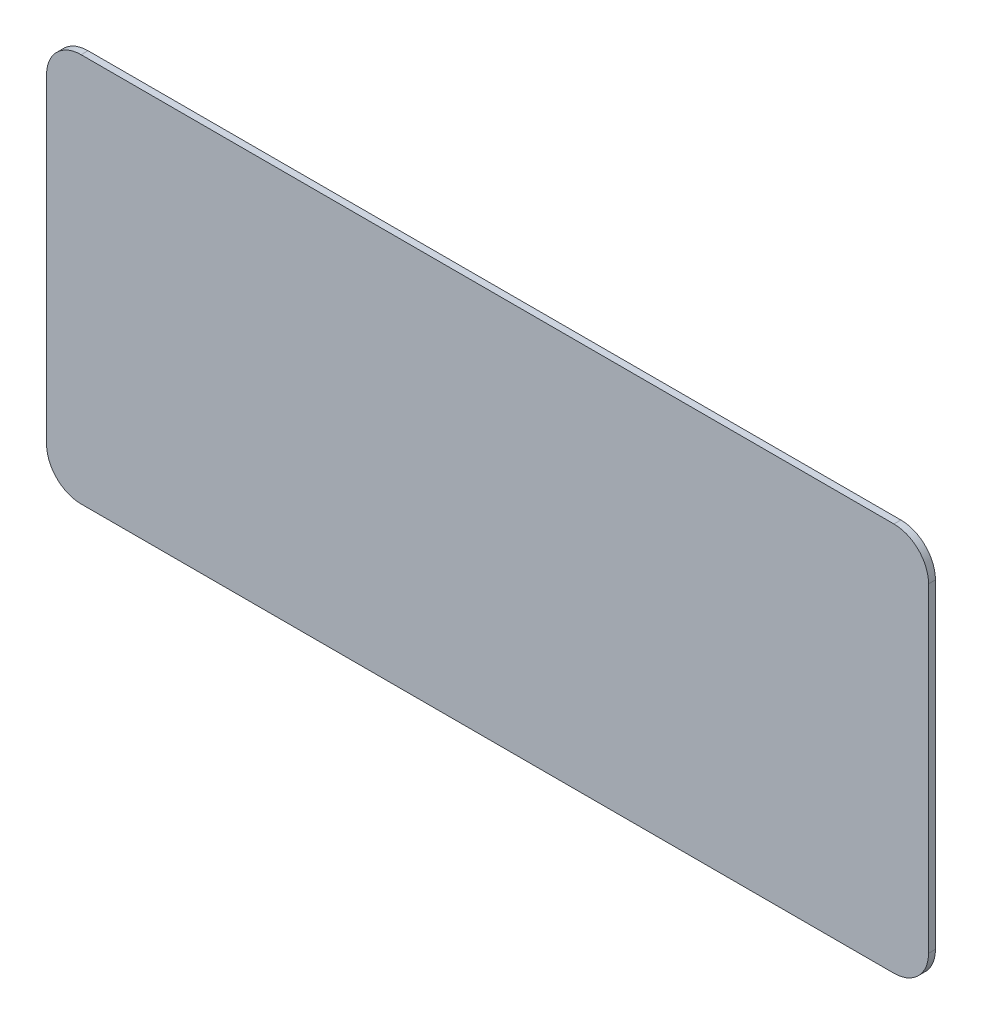
SolidWorks part; units mm, degrees
material "Acrylic (Medium-high impact)"
ref_plane "Front Plane" through (0, 0, 0) normal (0, 0, 1) x (1, 0, 0)
ref_plane "Top Plane" through (0, 0, 0) normal (0, 1, 0) x (1, 0, 0)
ref_plane "Right Plane" through (0, 0, 0) normal (1, 0, 0) x (0, 0, -1)
sketch "Sketch1" plane through (0, 0, 0) normal (0, 0, 1) x (1, 0, 0)
  line L1 (-250, -107.5) -> (250, -107.5) construction
  line L2 (-250, -107.5) -> (-250, 107.5) construction
  line L3 (-250, 107.5) -> (250, 107.5) construction
  line L4 (250, -107.5) -> (250, 107.5) construction
  line L5 (-250, -107.5) -> (250, 107.5) construction
  line L6 (-250, 107.5) -> (250, -107.5) construction
  line L7 (-255, -112.5) -> (255, -112.5)
  line L8 (-255, -112.5) -> (-255, 112.5)
  line L9 (-255, 112.5) -> (255, 112.5)
  line L10 (255, -112.5) -> (255, 112.5)
  line L11 (-255, -112.5) -> (255, 112.5) construction
  line L12 (-255, 112.5) -> (255, -112.5) construction
  point P0 (0, 0)
  dimension "D1" = 500
  dimension "D2" = 215
  dimension "D3" = 5
  dimension "D4" = 5
extrude "Boss-Extrude1" add sketch "Sketch1" along normal blind 4
fillet "Fillet1" radius 20 4 edges at (-255, -112.5, 2) (-255, 112.5, 2) (255, 112.5, 2) (255, -112.5, 2)
